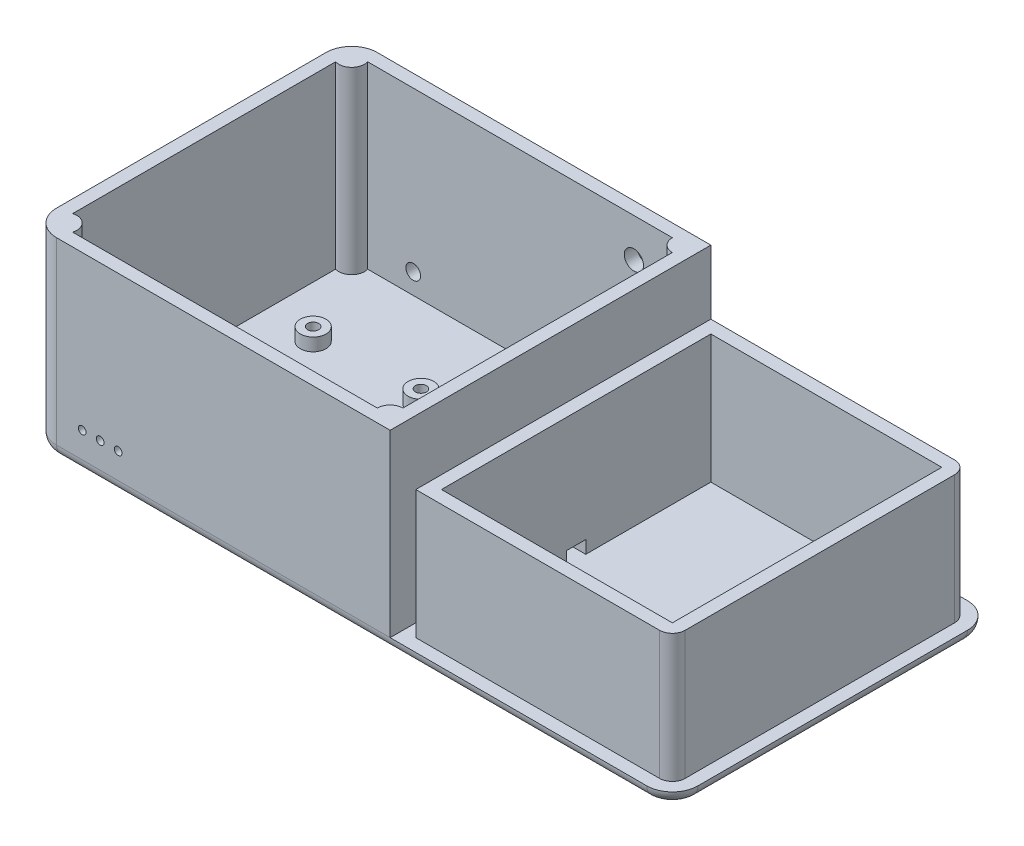
SolidWorks part; units mm, degrees
material "Custom Plastic"
ref_plane "Front Plane" through (0, 0, 0) normal (0, 0, 1) x (1, 0, 0)
ref_plane "Top Plane" through (0, 0, 0) normal (0, 1, 0) x (1, 0, 0)
ref_plane "Right Plane" through (0, 0, 0) normal (1, 0, 0) x (0, 0, -1)
sketch "Sketch1" plane through (0, 0, 0) normal (0, 1, 0) x (1, 0, 0)
  line L1 (-115, -62.5) -> (115, -62.5)
  line L2 (-125, -52.5) -> (-125, 52.5)
  line L3 (-115, 62.5) -> (115, 62.5)
  line L4 (125, -52.5) -> (125, 52.5)
  line L5 (-125, -62.5) -> (125, 62.5) construction
  line L6 (-125, 62.5) -> (125, -62.5) construction
  arc A0 (-115, -62.5) -> (-125, -52.5) centre (-115, -52.5) cw
  arc A1 (115, -62.5) -> (125, -52.5) centre (115, -52.5) ccw
  arc A2 (115, 62.5) -> (125, 52.5) centre (115, 52.5) cw
  arc A3 (-125, 52.5) -> (-115, 62.5) centre (-115, 52.5) cw
  point P0 (0, 0)
  dimension "D3" = 10
  dimension "D1" = 250
  dimension "D2" = 125
extrude "Boss-Extrude1" add sketch "Sketch1" along normal blind 5
fillet "Fillet1" radius 5 8 edges at (0, 0, 62.5) (122.0711, 0, 59.5711) (125, 0, 0) (122.0711, 0, -59.5711) (0, 0, -62.5) (-122.0711, 0, -59.5711) (-125, 0, 0) (-122.0711, 0, 59.5711)
sketch "Sketch2" plane through (0, 5, 0) normal (0, 1, 0) x (1, 0, 0)
  line L0 (-115, -57.5) -> (115, -57.5)
  line L1 (120, -52.5) -> (120, 52.5)
  line L2 (115, 57.5) -> (-115, 57.5)
  line L3 (-120, 52.5) -> (-120, -52.5)
  line L4 (-115, -62.5) -> (115, -62.5)
  line L5 (-115, -62.5) -> (115, -62.5)
  line L6 (125, -52.5) -> (125, 52.5)
  line L7 (125, -52.5) -> (125, 52.5)
  line L12 (15, 62.5) -> (15, -62.5)
  line L13 (10, 62.5) -> (10, -62.5)
  line L14 (20, 57.5) -> (20, -57.5)
  line L15 (115, 52.5) -> (20, 52.5)
  line L16 (115, 62.5) -> (-115, 62.5)
  line L17 (115, 62.5) -> (-115, 62.5)
  line L18 (-125, 52.5) -> (-125, -52.5)
  line L19 (-125, 52.5) -> (-125, -52.5)
  line L20 (115, 52.5) -> (115, -52.5)
  line L21 (115, -52.5) -> (20, -52.5)
  line L22 (20, 52.5) -> (20, -52.5)
  line L23 (25, 57.5) -> (25, -57.5)
  arc A0 (115, -57.5) -> (120, -52.5) centre (115, -52.5) ccw
  arc A1 (120, 52.5) -> (115, 57.5) centre (115, 52.5) ccw
  arc A2 (-115, 57.5) -> (-120, 52.5) centre (-115, 52.5) ccw
  arc A3 (-120, -52.5) -> (-115, -57.5) centre (-115, -52.5) ccw
  arc A4 (-125, -52.5) -> (-115, -62.5) centre (-115, -52.5) ccw
  arc A5 (-125, -52.5) -> (-115, -62.5) centre (-115, -52.5) ccw
  arc A6 (115, -62.5) -> (125, -52.5) centre (115, -52.5) ccw
  arc A7 (115, -62.5) -> (125, -52.5) centre (115, -52.5) ccw
  arc A16 (125, 52.5) -> (115, 62.5) centre (115, 52.5) ccw
  arc A17 (125, 52.5) -> (115, 62.5) centre (115, 52.5) ccw
  arc A18 (-115, 62.5) -> (-125, 52.5) centre (-115, 52.5) ccw
  arc A19 (-115, 62.5) -> (-125, 52.5) centre (-115, 52.5) ccw
  arc M25 (-125, -52.5) -> (-115, -62.5) centre (-115, -52.5) ccw
  line M26 (-115, -62.5) -> (115, -62.5)
  line M30 (115, 62.5) -> (-115, 62.5)
  arc M31 (-115, 62.5) -> (-125, 52.5) centre (-115, 52.5) ccw
  line M32 (-125, 52.5) -> (-125, -52.5)
  dimension "D8" = 5
  dimension "D10" = 5
  dimension "D11" = 5
  dimension "D13" = 5
  dimension "D2" = 5
  dimension "D3" = 5
  dimension "D4" = 5
  dimension "D5" = 5
  dimension "D6" = 5
  dimension "D7" = 5
  dimension "D9" = 5
  dimension "D12" = 5
  dimension "D14" = 5
  dimension "D15" = 140
  dimension "D16" = 5
  dimension "D17" = 5
extrude "Boss-Extrude2" add sketch "Sketch2" along normal blind 70 contours L2 L13 L0 L12 | L0 L13 L5 L12 | A3 L3 A2 L2 L13 L0 M30 M31 M32 M25 M26 | L13 L2 L12 M30 region at (12.5, 5, 60) region at (12.5, 5, 0) region at (8.1602, 5, 60) region at (12.5, 5, -60)
extrude "Boss-Extrude3" add sketch "Sketch2<3>" along normal blind 50 contours L23 L15 L14 L21 | L1 A1 L2 L23 L15 L20 L21 L0 A0 | L23 L2 L14 L15 | L23 L21 L14 L0 region at (22.5, 5, 55) region at (26.4916, 5, 55) region at (22.5, 5, 0) region at (22.5, 5, -55)
sketch "Sketch2<3>" plane through (0, 5, 0) normal (0, 1, 0) x (1, 0, 0) same geometry as "Sketch2"
sketch "Sketch3" plane through (0, 75, 0) normal (0, 1, 0) x (1, 0, 0)
  line L0 (15, 62.5) -> (15, -62.5) construction
  line L1 (15, 62.5) -> (15, -62.5) construction
  circle A0 centre (-118.5355, 56.0355) radius 5
  arc A1 (-115, 57.5) -> (-120, 52.5) centre (-115, 52.5) ccw construction
  circle A2 centre (10, 57.5) radius 5
  circle A3 centre (10, -57.5) radius 5
  circle A4 centre (-118.5355, -56.0355) radius 5
  arc A5 (-120, -52.5) -> (-115, -57.5) centre (-115, -52.5) ccw construction
  arc A6 (-125, -52.5) -> (-115, -62.5) centre (-115, -52.5) ccw construction
extrude "Boss-Extrude4" add sketch "Sketch3" against normal up to surface (70 mm away) up to face at (-75.3452, 5, 0)
sketch "Sketch4" plane through (10, 0, 0) normal (-1, 0, 0) x (0, 0, 1)
  line L0 (52.5, 5) -> (-52.5, 5) construction
  line L1 (3.75, 10) -> (-3.75, 10)
  line L2 (3.75, 10) -> (3.75, 5)
  line L3 (3.75, 5) -> (-3.75, 5)
  line L4 (-3.75, 10) -> (-3.75, 5)
  line L5 (3.75, 10) -> (-3.75, 5) construction
  line L6 (3.75, 5) -> (-3.75, 10) construction
  point P0 (0, 7.5)
  point P7 (0, 0)
  dimension "D1" = 5
  dimension "D2" = 7.5
extrude "Cut-Extrude1" cut sketch "Sketch4" against normal up to surface (15 mm away) up to face at (25, 30, 0)
sketch "Sketch5" plane through (0, 0, -57.5) normal (0, 0, 1) x (1, 0, 0)
  line L0 (5, 5) -> (-113.7548, 5) construction
  line L1 (-120, 75) -> (-120, 5) construction
  line L2 (5, 75) -> (-113.7548, 75) construction
  line L3 (5, 75) -> (5, 5) construction
  circle A0 centre (-96, 13) radius 2.875
  circle A1 centre (-10, 60) radius 3.75
  dimension "D1" = 5.75
  dimension "D4" = 7.5
  dimension "D2" = 8
  dimension "D3" = 24
  dimension "D5" = 15
  dimension "D6" = 15
extrude "Cut-Extrude2" cut sketch "Sketch5" against normal up to surface (5 mm away) up to face at (-50, 40, -62.5)
sketch "Sketch6" plane through (0, 0, 62.5) normal (0, 0, 1) x (1, 0, 0)
  line L0 (-115, 75) -> (-115, 5) construction
  line L1 (-115, 5) -> (15, 5) construction
  circle A0 centre (-105, 15) radius 1.5
  circle A1 centre (-98, 15) radius 1.5
  circle A2 centre (-91, 15) radius 1.5
  dimension "D1" = 3
  dimension "D5" = 7
  dimension "D2" = 10
  dimension "D3" = 10
  dimension "D4" = 3
extrude "Cut-Extrude3" cut sketch "Sketch6" against normal up to surface (5 mm away) up to face at (-54.3774, 40, 57.5)
sketch "Sketch8" plane through (0, 5, 0) normal (0, 1, 0) x (1, 0, 0)
  line L0 (-113.7548, -57.5) -> (5, -57.5) construction
  line L1 (-120, 51.2548) -> (-120, -51.2548) construction
  circle A0 centre (-100, -37.5) radius 5
  circle A1 centre (-58, -37.5) radius 5
  circle A2 centre (-58, 22.5) radius 5
  circle A3 centre (-100, 22.5) radius 5
  circle A4 centre (-100, -37.5) radius 2.15
  circle A5 centre (-58, -37.5) radius 2.15
  circle A6 centre (-58, 22.5) radius 2.15
  circle A7 centre (-100, 22.5) radius 2.15
  dimension "D1" = 10
  dimension "D4" = 20
  dimension "D5" = 60
  dimension "D6" = 42
  dimension "D7" = 20
  dimension "D8" = 4.3
  dimension "D2" = 2
  dimension "D3" = 2
extrude "Boss-Extrude5" add sketch "Sketch8" along normal blind 5
equation "\"device_length\"=250"
equation "\"D1@Sketch1\"=\"device_length\""
equation "\"device_width\"=125"
equation "\"D2@Sketch1\"=\"device_width\""
equation "\"device_wall\"=5"
equation "\"D2@Sketch2\"=\"device_wall\""
equation "\"device_base\"= 5"
equation "\"D1@Boss-Extrude1\"=\"device_base\""
equation "\"D1@Fillet1\"=\"device_base\""
equation "\"D3@Sketch2\"=\"device_wall\""
equation "\"D4@Sketch2\"=\"device_wall\""
equation "\"D5@Sketch2\"=\"device_wall\""
equation "\"D6@Sketch2\"=\"device_wall\""
equation "\"D7@Sketch2\"=\"device_wall\""
equation "\"D8@Sketch2\"=\"device_wall\""
equation "\"D9@Sketch2\"=\"device_wall\""
equation "\"D10@Sketch2\"=\"device_wall\""
equation "\"D11@Sketch2\"=\"device_wall\""
equation "\"D12@Sketch2\"=\"device_wall\""
equation "\"D13@Sketch2\"=\"device_wall\""
equation "\"D14@Sketch2\"=\"device_wall\""
equation "\"main_length\"=140"
equation "\"D15@Sketch2\"=\"main_length\""
equation "\"device_height\"=75"
equation "\"D1@Boss-Extrude2\"=\"device_height\"-\"device_base\""
equation "\"D16@Sketch2\"=\"device_wall\""
equation "\"D17@Sketch2\"=\"device_wall\""
equation "\"inner_black_box\"=50"
equation "\"D1@Boss-Extrude3\"=\"inner_black_box\""
equation "\"D6@Sketch5\"=\"D5@Sketch5\""
